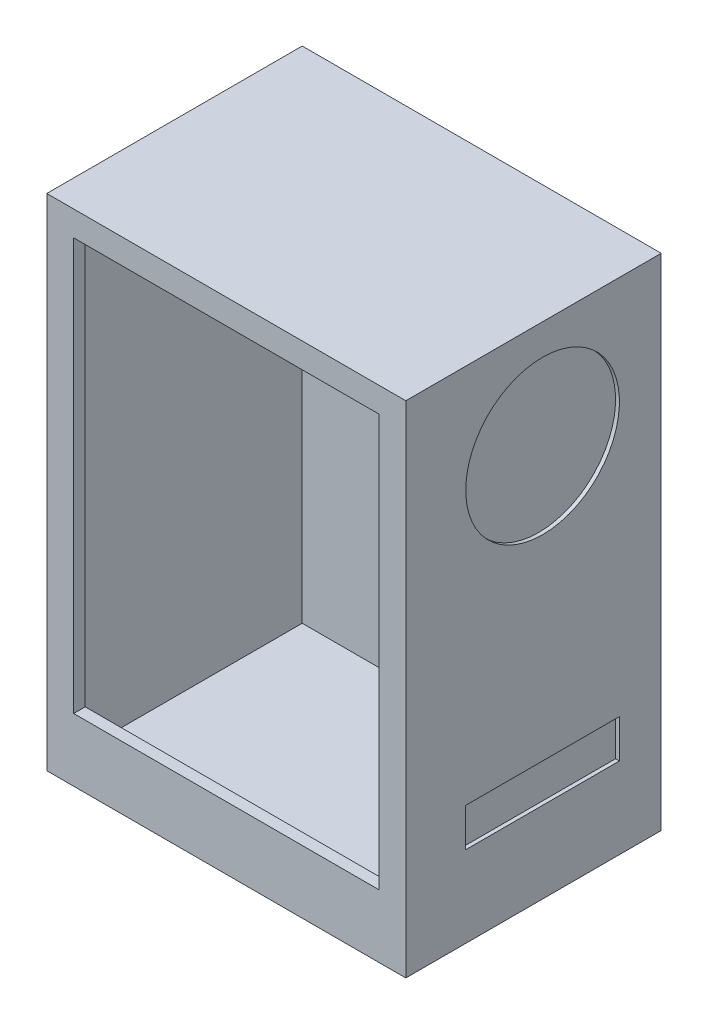
SolidWorks part; units mm, degrees
ref_plane "Front Plane" through (0, 0, 0) normal (0, 0, 1) x (1, 0, 0)
ref_plane "Top Plane" through (0, 0, 0) normal (0, 1, 0) x (1, 0, 0)
ref_plane "Right Plane" through (0, 0, 0) normal (1, 0, 0) x (0, 0, -1)
sketch "Sketch1" plane through (0, 0, 0) normal (0, 0, 1) x (1, 0, 0)
  line L0 (-19.86, 26.805) -> (-19.86, -26.805)
  line L5 (-18.86, 25.805) -> (18.86, 25.805) construction
  line L6 (-18.86, 25.805) -> (-18.86, -25.805) construction
  line L7 (-18.86, -25.805) -> (18.86, -25.805) construction
  line L8 (18.86, 25.805) -> (18.86, -25.805) construction
  line L9 (-19.86, -26.805) -> (19.86, -26.805)
  line L10 (-21.86, 28.555) -> (-21.86, 30.055) construction
  line L11 (-21.86, 28.555) -> (21.86, 28.555)
  line L12 (-21.86, 28.555) -> (-21.86, -33.505)
  line L13 (-21.86, -33.505) -> (21.86, -33.505)
  line L14 (21.86, 28.555) -> (21.86, -33.505)
  line L15 (-23.36, 30.055) -> (23.36, 30.055)
  line L16 (-23.36, 30.055) -> (-23.36, -35.005)
  line L17 (-23.36, -35.005) -> (23.36, -35.005)
  line L18 (23.36, 30.055) -> (23.36, -35.005)
  line L19 (-21.86, 28.555) -> (-23.36, 28.555) construction
  line L20 (21.86, -33.505) -> (21.86, -35.005) construction
  line L21 (21.86, -33.505) -> (23.36, -33.505) construction
  line L22 (-21.36, 28.055) -> (-21.36, 28.555) construction
  line L23 (-21.36, 28.055) -> (-21.86, 28.055) construction
  line L24 (21.36, -32.205) -> (21.86, -32.205) construction
  line L25 (-13.25, -33.005) -> (-13.25, -33.505) construction
  line L26 (19.86, 26.805) -> (19.86, -26.805)
  line L27 (-19.86, 26.805) -> (19.86, 26.805)
  point P0 (-0.1235, 1.305)
  dimension "D1" = 1
  dimension "D2" = 1.5
  dimension "D3" = 0.5
extrude "Boss-Extrude1" add sketch "Sketch1" along normal blind 1.5 contours L14 L11 L12 L13 L5 L8 L7 L6 | L18 L15 L16 L17 L11 L14 L13 L12 region at (0, 27.7959, 0) region at (0, 29.254, 0)
extrude "Boss-Extrude2" add sketch "Sketch1<3>" against normal up to surface (30.24 mm away) contours L18 L15 L16 L17 L11 L14 L13 L12 region at (0, 29.254, 0)
sketch "Sketch1<3>" plane through (0, 0, 0) normal (0, 0, 1) x (1, 0, 0) same geometry as "Sketch1"
sketch "Sketch3" plane through (0, 0, -30.24) normal (0, 0, -1) x (-1, 0, 0)
  line L0 (6.092, 26.355) -> (-19.613, 26.355)
  line L1 (5.092, -23.195) -> (-18.613, -23.195) construction
  line L2 (5.092, -23.195) -> (5.092, 25.355) construction
  line L3 (5.092, 25.355) -> (-18.613, 25.355) construction
  line L4 (-18.613, -23.195) -> (-18.613, 25.355) construction
  line L5 (-19.613, -24.195) -> (-19.613, 26.355)
  line L6 (6.092, -24.195) -> (-19.613, -24.195)
  line L7 (6.092, -24.195) -> (6.092, 26.355)
  line L9 (-23.36, 30.055) -> (23.36, 30.055)
  line L10 (-23.36, 30.055) -> (-23.36, -35.005)
  line L11 (-23.36, -35.005) -> (23.36, -35.005)
  line L12 (23.36, 30.055) -> (23.36, -35.005)
  line M13 (-21.86, 28.555) -> (21.86, 28.555)
  line M14 (21.86, 28.555) -> (21.86, -33.505)
  line M15 (21.86, -33.505) -> (-21.86, -33.505)
  line M16 (-21.86, -33.505) -> (-21.86, 28.555)
  line M17 (23.36, 30.055) -> (-23.36, 30.055)
  line M18 (-23.36, 30.055) -> (-23.36, -35.005)
  line M19 (-23.36, -35.005) -> (23.36, -35.005)
  line M20 (23.36, -35.005) -> (23.36, 30.055)
  dimension "D1" = 1
extrude "Boss-Extrude3" add sketch "Sketch3" along normal blind 1.5 contours L7 L6 L5 L0 M13 M16 M15 M14 | M20 M17 M18 M19 M16 M13 M14 M15 region at (0, 29.254, -30.24) region at (-6.2131, -5.7421, -30.24)
sketch "Sketch4" plane through (23.36, 0, 0) normal (1, 0, 0) x (0, 0, -1)
  line L1 (6.3, -19.445) -> (26.3, -19.445)
  line L2 (6.3, -19.445) -> (6.3, -24.445)
  line L3 (6.3, -24.445) -> (26.3, -24.445)
  line L4 (26.3, -19.445) -> (26.3, -24.445)
  circle A0 centre (16.3, 16.055) radius 10
  circle A1 centre (16.3, 16.055) radius 10 construction
extrude "Cut-Extrude1" cut sketch "Sketch4" against normal blind 0.5
